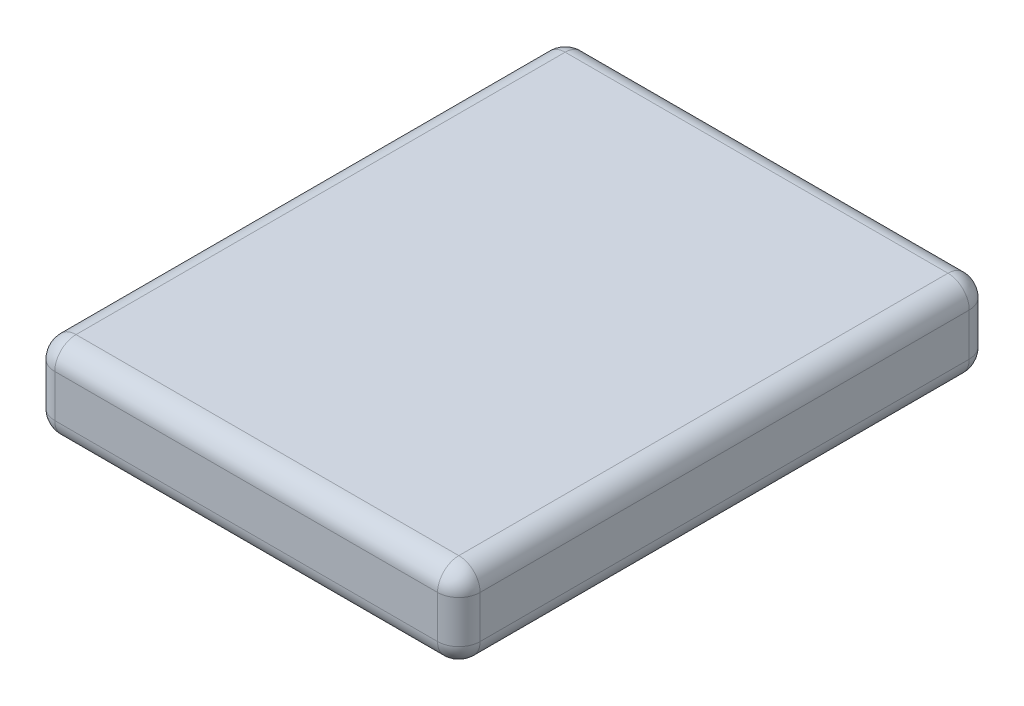
SolidWorks part; units mm, degrees
ref_plane "前视基准面" through (0, 0, 0) normal (0, 0, 1) x (1, 0, 0)
ref_plane "上视基准面" through (0, 0, 0) normal (0, 1, 0) x (1, 0, 0)
ref_plane "右视基准面" through (0, 0, 0) normal (1, 0, 0) x (0, 0, -1)
sketch "草图1" plane through (0, 0, 0) normal (0, 1, 0) x (1, 0, 0)
  line L1 (-10, 12.5) -> (10, 12.5)
  line L2 (-10, 12.5) -> (-10, -12.5)
  line L3 (-10, -12.5) -> (10, -12.5)
  line L4 (10, 12.5) -> (10, -12.5)
  line L5 (-10, 12.5) -> (10, -12.5) construction
  line L6 (-10, -12.5) -> (10, 12.5) construction
  point P0 (0, 0)
extrude "凸台-拉伸1" add sketch "草图1" along normal blind 4
fillet "圆角2" radius 1 7 edges at (10, 0, 0) (0, 0, -12.5) (-10, 2, -12.5) (-10, 0, 0) (-10, 4, 0) (-10, 2, 12.5) (0, 0, 12.5)
fillet "圆角3" radius 1 9 edges at (9.7071, 0.2929, -12.2071) (9.7071, 0.2929, 12.2071) (-9.7071, 3.7071, -12.2071) (-9.7071, 3.7071, 12.2071) (10, 4, 0) (10, 2.5, -12.5) (10, 2.5, 12.5) (0.5, 4, -12.5) (0.5, 4, 12.5)
sketch "草图3" plane through (0, 0, 0) normal (0, 1, 0) x (1, 0, 0)
  line L1 (0, -2.2) -> (0, 2.2) construction
  circle A0 centre (-10.5, 13.5) radius 0.75
  circle A3 centre (10.5, 13.5) radius 0.75
